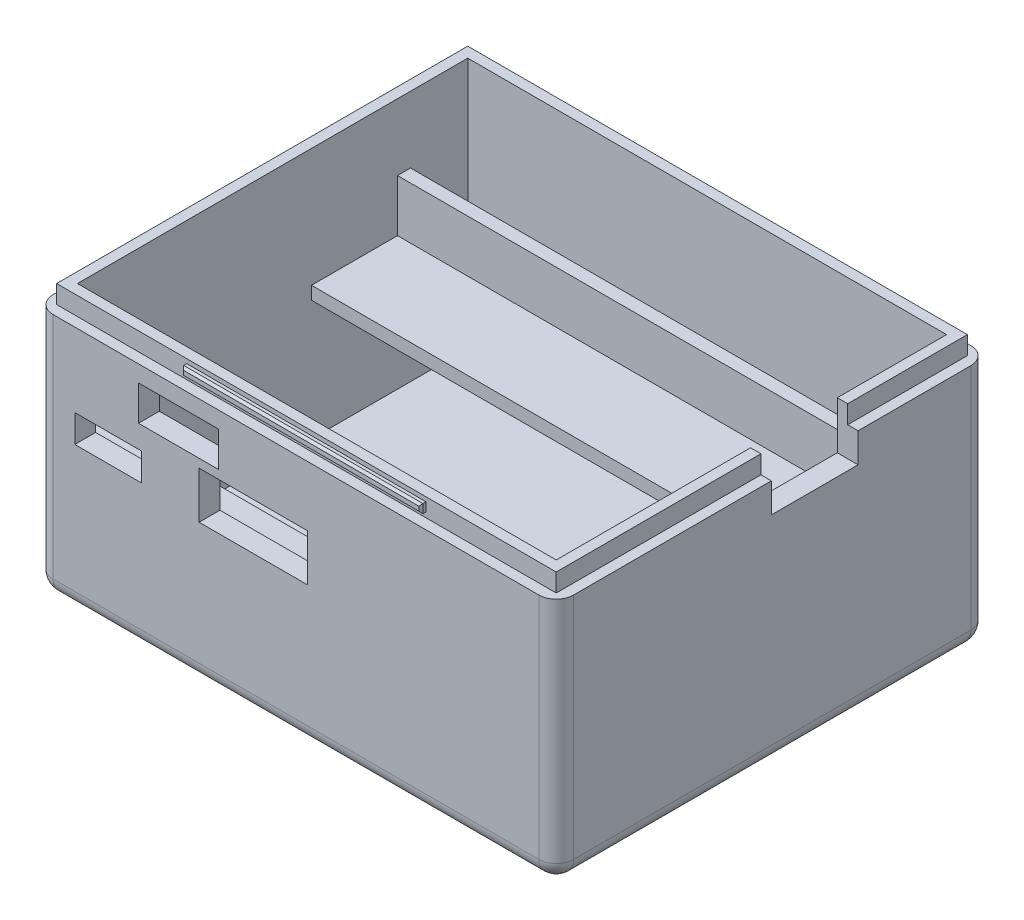
SolidWorks part; units mm, degrees
ref_plane "Front Plane" through (0, 0, 0) normal (0, 0, 1) x (1, 0, 0)
ref_plane "Top Plane" through (0, 0, 0) normal (0, 1, 0) x (1, 0, 0)
ref_plane "Right Plane" through (0, 0, 0) normal (1, 0, 0) x (0, 0, -1)
sketch "BatteryAndOuterWalls" plane through (0, 0, 0) normal (0, 1, 0) x (1, 0, 0)
  line L0 (30, -24.9) -> (30, 24.9)
  line L1 (27.6, -22.5) -> (-27.6, -22.5)
  line L2 (27.6, -22.5) -> (27.6, 22.5)
  line L3 (27.6, 22.5) -> (-27.6, 22.5)
  line L4 (-27.6, -22.5) -> (-27.6, 22.5)
  line L5 (27.6, -22.5) -> (-27.6, 22.5) construction
  line L6 (27.6, 22.5) -> (-27.6, -22.5) construction
  line L7 (30, 24.9) -> (-30, 24.9)
  line L8 (-30, -24.9) -> (-30, 24.9)
  line L9 (30, -24.9) -> (-30, -24.9)
  point P0 (0, 0)
  dimension "D1" = 55.2
  dimension "D2" = 45
  dimension "D4" = 60
  dimension "D5" = 49.8
  dimension "D3" = 2.4
extrude "Walls" add sketch "BatteryAndOuterWalls" along normal blind 29
sketch "SinkRim" plane through (0, 29, 0) normal (0, 1, 0) x (1, 0, 0)
  line L0 (-28.8, 23.7) -> (-28.8, -23.7)
  line L5 (-27.6, 22.5) -> (27.6, 22.5)
  line L6 (-27.6, 22.5) -> (-27.6, -22.5)
  line L7 (-27.6, -22.5) -> (27.6, -22.5)
  line L8 (27.6, 22.5) -> (27.6, -22.5)
  line L9 (-28.8, -23.7) -> (28.8, -23.7)
  line L10 (28.8, 23.7) -> (28.8, -23.7)
  line L11 (-28.8, 23.7) -> (28.8, 23.7)
  line L12 (-30, 24.9) -> (30, 24.9)
  line L13 (30, 24.9) -> (30, -24.9)
  line L14 (-30, -24.9) -> (30, -24.9)
  line L15 (-30, 24.9) -> (-30, -24.9)
  line M5 (-30, -24.9) -> (30, -24.9)
  line M6 (30, -24.9) -> (30, 24.9)
  line M7 (30, 24.9) -> (-30, 24.9)
  line M8 (-30, 24.9) -> (-30, -24.9)
  dimension "D1" = 1.2
  dimension "D2" = 1.2
sketch "Sketch2" plane through (0, 0, 0) normal (0, -1, 0) x (1, 0, 0)
  line L0 (-30, 24.9) -> (30, 24.9) construction
  line L5 (-30, 24.9) -> (30, 24.9)
  line L6 (-30, 24.9) -> (-30, -24.9)
  line L7 (-30, -24.9) -> (30, -24.9)
  line L8 (30, 24.9) -> (30, -24.9)
  line L9 (-30, -24.9) -> (-30, 24.9) construction
extrude "Bottom" add sketch "Sketch2" along normal blind 1.5
extrude "Top-Cut" cut sketch "SinkRim" against normal blind 2.1 contours L0 L11 L10 L9 M8 M5 M6 M7 region at (0, 29, -24.1203)
sketch "FrontRail" plane through (30, 0, 0) normal (1, 0, 0) x (0, 0, -1)
  line L0 (13.6255, 19.3303) -> (-12.2825, 19.3303) construction
  line L1 (-22.5132, 29) -> (22.5, 29)
  line L3 (-22.5132, 0) -> (22.5, 0)
  line L4 (22.5, 29) -> (22.5, 0)
  line L5 (24.9, -1.5) -> (-24.9, -1.5) construction
  line L6 (24.9, 26.9) -> (24.9, -1.5) construction
  line L7 (23.7, 29) -> (-23.7, 29) construction
  line L8 (-22.5132, 0) -> (-22.5132, 29)
  line L31 (-22.5132, 12.5) -> (-19.5132, 12.5)
  line L36 (-22.5132, 12.5) -> (-22.5132, 14)
  line L37 (-22.5132, 14) -> (-19.5132, 14)
  line L38 (-19.5132, 12.5) -> (-19.5132, 14)
  line L39 (-4.5132, 15.3303) -> (22.5, 15.3303)
  line L40 (-4.5132, 15.3303) -> (-4.5132, 13.8303)
  line L41 (-4.5132, 13.8303) -> (22.5, 13.8303)
  line L42 (22.5, 15.3303) -> (22.5, 13.8303)
  line L44 (14.4, 15.3303) -> (15.9, 15.3303)
  line L45 (14.4, 15.3303) -> (14.4, 21.3303)
  line L46 (14.4, 21.3303) -> (15.9, 21.3303)
  line L47 (15.9, 15.3303) -> (15.9, 21.3303)
  dimension "D10" = 0
  dimension "D6" = 3
  dimension "D1" = 12.5
  dimension "D2" = 1.5
  dimension "D3" = 2.4
  dimension "D4" = 0
  dimension "D5" = 1.5
  dimension "D7" = 1.5
  dimension "D8" = 4
  dimension "D9" = 15
  dimension "D11" = 6
  dimension "D12" = 0
  dimension "D13" = 1.5
  dimension "D14" = 8.1
  dimension "D15" = 6.6
extrude "PCB-Supports" add sketch "FrontRail" against normal blind 60 contours L41 L42 L39 L40 | L37 L38 L31 L36 | L45 L44 L47 L46
sketch "Sketch3" plane through (0, 0, 0) normal (0, 1, 0) x (1, 0, 0)
  line L1 (-27.6, 22.5) -> (27.6, 22.5)
  line L2 (-27.6, 22.5) -> (-27.6, -22.5)
  line L3 (-27.6, -22.5) -> (27.6, -22.5)
  line L4 (27.6, 22.5) -> (27.6, -22.5)
  line L5 (27.6, 22.5) -> (-27.6, 22.5)
  line L6 (27.6, 22.5) -> (27.6, 15.9)
  line L7 (27.6, 15.9) -> (-27.6, 15.9)
  line L8 (-27.6, 22.5) -> (-27.6, 15.9)
  line L9 (-27.6, -4.5132) -> (27.6, -4.5132)
  line L10 (-27.6, -4.5132) -> (-27.6, 4.4868)
  line L11 (-27.6, 4.4868) -> (27.6, 4.4868)
  line L12 (27.6, -4.5132) -> (27.6, 4.4868)
  dimension "D1" = 9
  dimension "D2" = 6.6
extrude "Battery-Insertion-Cut" cut sketch "Sketch3" along normal blind 25 contours L7 L4 L1 L2 | L11 L12 L9 L10 region at (0, 0, -19.2)
sketch "USB_FRONT" plane through (0, 0, 24.9) normal (0, 0, 1) x (1, 0, 0)
  line L0 (-30, 26.9) -> (30, 26.9) construction
  line L1 (-25.5021, 15.1801) -> (-17.8193, 15.1801)
  line L2 (-25.5021, 15.1801) -> (-25.5021, 18.3701)
  line L3 (-25.5021, 18.3701) -> (-17.8193, 18.3701)
  line L4 (-17.8193, 15.1801) -> (-17.8193, 18.3701)
  line L5 (-11.1723, 14.5801) -> (-11.1723, 19.9801)
  line L10 (-11.1723, 19.9801) -> (1.3277, 19.9801)
  line L11 (1.3277, 14.5801) -> (1.3277, 19.9801)
  line L12 (-11.1723, 14.5801) -> (1.3277, 14.5801)
  line L14 (-18.1623, 20.9683) -> (-8.9623, 20.9683)
  line L15 (-18.1623, 20.9683) -> (-18.1623, 25)
  line L16 (-18.1623, 25) -> (-8.9623, 25)
  line L17 (-8.9623, 20.9683) -> (-8.9623, 25)
  dimension "D1" = 1.9
  dimension "D2" = 0.9882
  dimension "D3" = 2.5982
  dimension "D4" = 9.2
  dimension "D5" = 5.9317
extrude "USB-Front-Cut" cut sketch "USB_FRONT" against normal blind 10
sketch "USB-Right-Sketch" plane through (30, 0, 0) normal (1, 0, 0) x (0, 0, -1)
  line L0 (24.9, 26.9) -> (24.9, -1.5) construction
  line L1 (-0.1, 29) -> (9.9, 29)
  line L2 (-0.1, 29) -> (-0.1, 23.5)
  line L3 (-0.1, 23.5) -> (9.9, 23.5)
  line L4 (9.9, 29) -> (9.9, 23.5)
  line L5 (23.7, 29) -> (-23.7, 29) construction
  line L6 (-24.9, 26.9) -> (24.9, 26.9) construction
  dimension "D1" = 0
  dimension "D2" = 5.5
  dimension "D3" = 15
  dimension "D4" = 10
  dimension "D5" = 3.4
extrude "USB-Side" cut sketch "USB-Right-Sketch" against normal blind 5
ref_plane "Plane1" through (0, 0, 0) normal (0, 0, 1) x (1, 0, 0)
sketch "Sketch7" plane through (0, 0, 23.7) normal (0, 0, 1) x (1, 0, 0)
  line L0 (-28.8, 29) -> (28.8, 29) construction
  line L1 (-13.8, 28.5) -> (13.8, 28.5)
  line L2 (-13.8, 28.5) -> (-13.8, 27.5)
  line L3 (-13.8, 27.5) -> (13.8, 27.5)
  line L4 (13.8, 28.5) -> (13.8, 27.5)
  line L5 (-30, 26.9) -> (30, 26.9) construction
  line L6 (-28.8, 26.9) -> (-28.8, 29) construction
  line L7 (28.8, 26.9) -> (28.8, 29) construction
  dimension "D1" = 0.5
  dimension "D2" = 1
  dimension "D3" = 0.6
  dimension "D4" = 15
  dimension "D5" = 15
extrude "Lid-Ridge-Front" add sketch "Sketch7" along normal blind 0.6
chamfer "Lid-Ridge-Front-Chamfer" distance 0.25 angle 45 4 edges at (0, 28.5, 24.3) (13.8, 28, 24.3) (0, 27.5, 24.3) (-13.8, 28, 24.3)
mirror "Mirror1" about plane through (0, 0, 0) normal (0, 0, 1) of "Lid-Ridge-Front-Chamfer", "Lid-Ridge-Front"
fillet "Fillet1" radius 2 8 edges at (0, -1.5, 24.9) (30, 12.7, 24.9) (-30, 12.7, 24.9) (-30, -1.5, 0) (-30, 12.7, -24.9) (0, -1.5, -24.9) (30, -1.5, 0) (30, 12.7, -24.9)
sketch "Sketch9" plane through (0, 0, 0) normal (1, 0, 0) x (0, 0, -1)
  line L0 (22.9, -1.5) -> (-22.9, -1.5) construction
  line L15 (-22.9, 26.9) -> (-22.9, 0.5) construction
  line L16 (-22.9, 5.5) -> (-33.9, 5.5)
  line L17 (-22.9, 5.5) -> (-22.9, -4.5)
  line L18 (-22.9, -4.5) -> (-33.9, -4.5)
  line L19 (-33.9, 5.5) -> (-33.9, -4.5)
  circle A0 centre (0, -124.5) radius 125
  circle A1 centre (0, -124.5) radius 131
  dimension "D4" = 250
  dimension "D7" = 6
  dimension "D1" = 10
  dimension "D2" = 3
  dimension "D3" = 123
  dimension "D5" = 11
  dimension "D6" = 6
